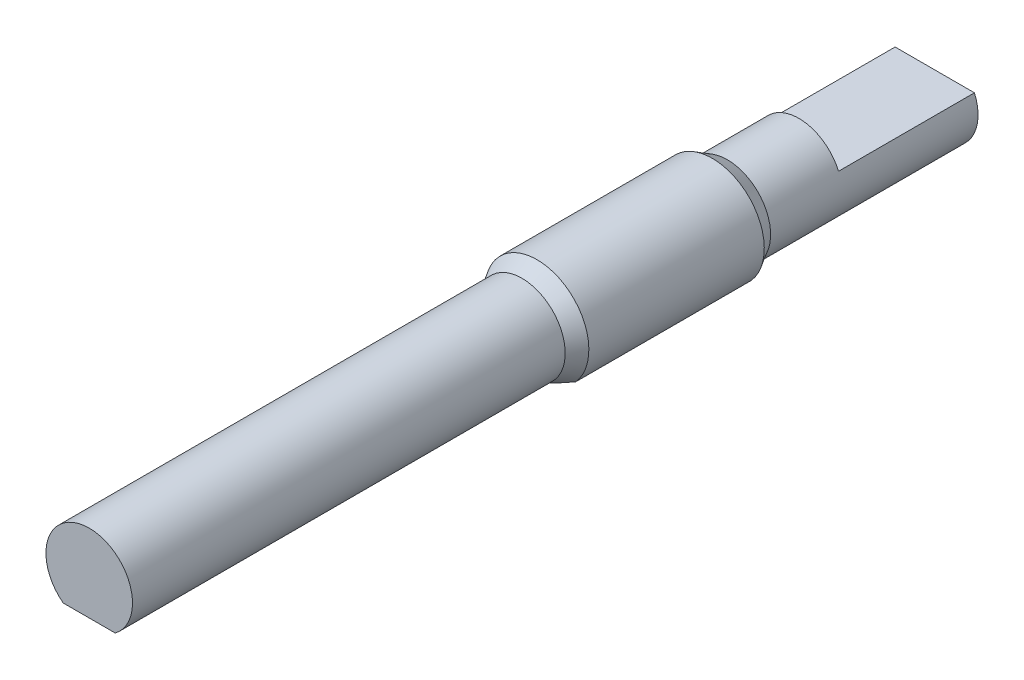
SolidWorks part; units mm, degrees
ref_plane "Front Plane" through (0, 0, 0) normal (0, 0, 1) x (1, 0, 0)
ref_plane "Top Plane" through (0, 0, 0) normal (0, 1, 0) x (1, 0, 0)
ref_plane "Right Plane" through (0, 0, 0) normal (1, 0, 0) x (0, 0, -1)
sketch "Sketch1" plane through (0, 0, 0) normal (0, 0, 1) x (1, 0, 0)
  circle A0 centre (0, 0) radius 2.5
  dimension "D1" = 5
extrude "Boss-Extrude1" add sketch "Sketch1" along normal blind 25
sketch "Sketch2" plane through (0, 0, 0) normal (0, 0, -1) x (-1, 0, 0)
  circle A0 centre (0, 0) radius 3
  dimension "D1" = 6
extrude "Boss-Extrude2" add sketch "Sketch2" along normal blind 11
chamfer "Chamfer1" distance 0.5 angle 60 1 edges at (-3, 0, 0) first distance on face at (2.5, 0, 0)
sketch "Sketch3" plane through (0, 0, -11) normal (0, 0, -1) x (-1, 0, 0)
  circle A0 centre (0, 0) radius 2.5
  dimension "D1" = 5
extrude "Boss-Extrude3" add sketch "Sketch3" along normal blind 5
chamfer "Chamfer3" distance 0.5 angle 60 1 edges at (-2.5, 0, -11) first distance on face at (-2.5, 0, -11)
sketch "Sketch4" plane through (0, 0, -16) normal (0, 0, -1) x (-1, 0, 0)
  line L0 (-2.2913, 1) -> (2.2913, 1)
  arc A0 (-2.2913, 1) -> (2.2913, 1) centre (0, 0) ccw
  dimension "D1" = 5
  dimension "D2" = 1.5
extrude "Boss-Extrude4" add sketch "Sketch4" along normal blind 7.85
ref_plane "Plane1" through (0, -2, 0) normal (0, 1, 0) x (1, 0, 0)
other "SurfaceCut1"
